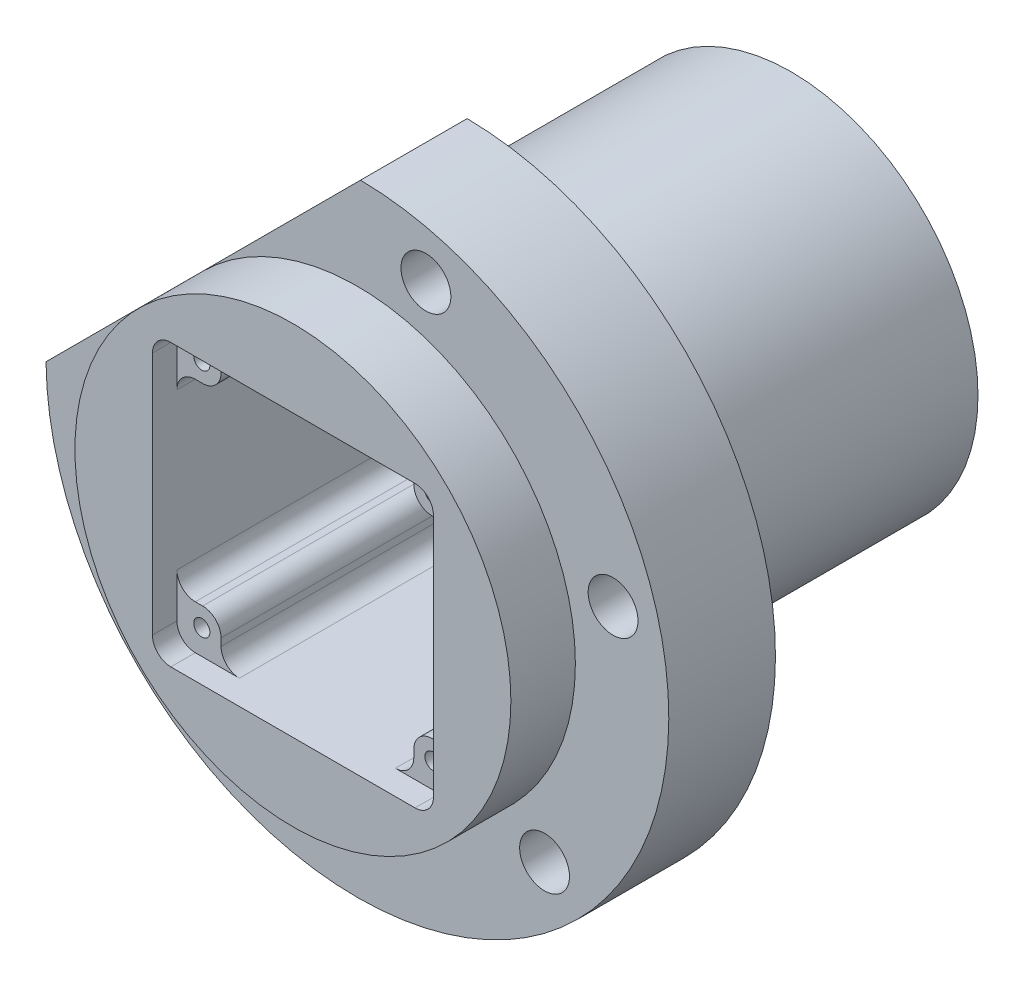
SolidWorks part; units mm, degrees
ref_plane "Front Plane" through (0, 0, 0) normal (0, 0, 1) x (1, 0, 0)
ref_plane "Top Plane" through (0, 0, 0) normal (0, 1, 0) x (1, 0, 0)
ref_plane "Right Plane" through (0, 0, 0) normal (1, 0, 0) x (0, 0, -1)
sketch "Sketch1" plane through (0, 0, 0) normal (0, 0, 1) x (1, 0, 0)
  circle A0 centre (0, 0) radius 44.45
  circle A1 centre (0, 0) radius 63.5
  dimension "D1" = 88.9
  dimension "D2" = 127
extrude "Boss-Extrude1" add sketch "Sketch1" along normal blind 6.35 contours A1 A0 | A0 region at (-61.7039, 0, 0)
extrude "Boss-Extrude2" add sketch "Sketch1<3>" against normal blind 101.6 from offset 19.5 contours A0 region at (0, 0, 0)
sketch "Sketch1<3>" plane through (0, 0, 0) normal (0, 0, 1) x (1, 0, 0) same geometry as "Sketch1"
sketch "Sketch2" plane through (0, 0, 19.5) normal (0, 0, -1) x (-1, 0, 0)
  line L0 (-19.65, 28.65) -> (-19.65, 19.65)
  line L1 (-28.65, -28.65) -> (28.65, -28.65) construction
  line L2 (-28.65, -28.65) -> (-28.65, 28.65) construction
  line L3 (-28.65, 28.65) -> (28.65, 28.65) construction
  line L4 (28.65, -28.65) -> (28.65, 28.65) construction
  line L5 (-28.65, -28.65) -> (28.65, 28.65) construction
  line L6 (-28.65, 28.65) -> (28.65, -28.65) construction
  line L7 (-19.65, 19.65) -> (-28.65, 19.65)
  line L8 (-28.65, 19.65) -> (-28.65, -19.65)
  line L9 (-28.65, -19.65) -> (-19.65, -19.65)
  line L10 (-19.65, -19.65) -> (-19.65, -28.65)
  line L11 (-19.65, -28.65) -> (19.65, -28.65)
  line L12 (19.65, -28.65) -> (19.65, -19.65)
  line L13 (19.65, -19.65) -> (28.65, -19.65)
  line L14 (28.65, -19.65) -> (28.65, 19.65)
  line L15 (28.65, 19.65) -> (19.65, 19.65)
  line L16 (19.65, 19.65) -> (19.65, 28.65)
  line L17 (19.65, 28.65) -> (-19.65, 28.65)
  point P0 (0, 0)
  dimension "D1" = 57.3
  dimension "D2" = 9
extrude "Cut-Extrude1" cut sketch "Sketch2" along normal through all
fillet "Fillet1" radius 3.75 12 edges at (19.65, -19.65, -31.3) (-19.65, -19.65, -31.3) (-19.65, 19.65, -31.3) (19.65, 19.65, -31.3) (-28.65, 19.65, -31.3) (-19.65, -28.65, -31.3) (19.65, -28.65, -31.3) (28.65, -19.65, -31.3) (28.65, 19.65, -31.3) (19.65, 28.65, -31.3) (-19.65, 28.65, -31.3) (-28.65, -19.65, -31.3)
sketch "Sketch3" plane through (0, 0, 19.5) normal (0, 0, -1) x (-1, 0, 0)
  line L1 (-24.9, -28.65) -> (24.9, -28.65)
  line L2 (-28.65, -24.9) -> (-28.65, 24.9)
  line L3 (-24.9, 28.65) -> (24.9, 28.65)
  line L4 (28.65, -24.9) -> (28.65, 24.9)
  line L5 (-28.65, -28.65) -> (28.65, 28.65) construction
  line L6 (-28.65, 28.65) -> (28.65, -28.65) construction
  arc A0 (-24.9, -28.65) -> (-28.65, -24.9) centre (-24.9, -24.9) cw
  arc A1 (24.9, -28.65) -> (28.65, -24.9) centre (24.9, -24.9) ccw
  arc A2 (24.9, 28.65) -> (28.65, 24.9) centre (24.9, 24.9) cw
  arc A3 (-28.65, 24.9) -> (-24.9, 28.65) centre (-24.9, 24.9) cw
  point P0 (0, 0)
  dimension "D2" = 3.75
  dimension "D1" = 57.3
extrude "Cut-Extrude2" cut sketch "Sketch3" along normal blind 5
sketch "Sketch4" plane through (0, 0, 0) normal (0, 0, -1) x (-1, 0, 0)
  circle A0 centre (0, 0) radius 44.45 construction
  circle A1 centre (0, 0) radius 63.5
  circle A2 centre (0, 0) radius 63.5
  circle A3 centre (0, 0) radius 44.45
  dimension "D1" = 0
extrude "Boss-Extrude3" add sketch "Sketch4" along normal blind 15.4
ref_plane "Plane1" through (0, 0, -7.4) normal (0, 0, -1) x (-1, 0, 0)
hole_wizard "CSK for #8 Flat Head Machine Screw1" positions "Sketch6" profile "Sketch7" countersink size "#8" standard "ANSI Inch" end condition through all
sketch "Sketch6" plane through (0, 0, -7.4) normal (0, 0, 1) x (1, 0, 0)
  line L0 (0, 0) -> (38.1661, -38.1661) construction
  line L2 (-24.9, 28.65) -> (24.9, 28.65) construction
  line L3 (31.4309, -31.4309) -> (44.9013, -44.9013) construction
  line L4 (0, 0) -> (38.1661, -38.1661) construction
  circle A0 centre (0, 0) radius 44.45 construction
  circle A1 centre (0, 0) radius 44.45 construction
  circle A4 centre (0, 0) radius 44.45 construction
  circle A5 centre (0, 0) radius 63.5
  circle A6 centre (0, 0) radius 63.5 construction
  point P0 (38.1661, -38.1661)
  point P45 (-13.9698, -52.1358)
  point P46 (-52.1358, -13.9698)
  point P47 (-38.1661, 38.1661)
  point P48 (13.9698, 52.1358)
  point P49 (52.1358, 13.9698)
  dimension "D1" = 45
  dimension "D2" = 6
sketch "Sketch7" plane through (38.1661, -38.1661, -7.4) normal (1, 0, 0) x (0, -1, 0)
  line L0 (0, 0) -> (0, 74.7)
  line L1 (0, 74.7) -> (2.2479, 74.7)
  line L2 (2.2479, 74.7) -> (2.2479, 3.2645)
  line L3 (2.2479, 3.2645) -> (5.0857, 0)
  line L5 (5.0857, 0) -> (0, 0)
  line L6 (-2.2479, 3.2645) -> (-5.0857, 0) construction
  line L11 (0, -6.35) -> (0, 107.95) construction
  dimension "Thru Hole Dia." = 4.4958
  dimension "Thru Hole Depth" = 74.7
  dimension "Near C'Sink Dia." = 10.1714
  dimension "Near C'Sink Angle" = 82
sketch "Sketch5" plane through (0, 0, 6.35) normal (0, 0, 1) x (1, 0, 0)
  line L0 (0.635, 63.4968) -> (-63.4968, -0.635)
  line L1 (-24.9, 28.65) -> (24.9, 28.65) construction
  circle A0 centre (0, 0) radius 63.5 construction
  circle A1 centre (0, 0) radius 44.45 construction
  circle A2 centre (0, 0) radius 63.5
  circle M3 centre (0, 0) radius 63.5
  dimension "D1" = 45
extrude "Cut-Extrude3" cut sketch "Sketch5" against normal through all contours L0 M3 region at (-36.895, 36.895, 6.35)
sketch "Sketch8" plane through (0, 0, -7.4) normal (0, 0, -1) x (-1, 0, 0)
  circle A4 centre (-38.1661, -38.1661) radius 5.0857 construction
  circle A9 centre (-38.1661, -38.1661) radius 5.0857
  circle A10 centre (52.1358, -13.9698) radius 5.0857 construction
  circle A11 centre (13.9698, -52.1358) radius 5.0857 construction
  circle A12 centre (-52.1358, 13.9698) radius 5.0857 construction
  circle A13 centre (-13.9698, 52.1358) radius 5.0857 construction
  circle A14 centre (52.1358, -13.9698) radius 5.0857
  circle A15 centre (13.9698, -52.1358) radius 5.0857
  circle A16 centre (-52.1358, 13.9698) radius 5.0857
  circle A17 centre (-13.9698, 52.1358) radius 5.0857
extrude "Cut-Extrude4" cut sketch "Sketch8" against normal through all
hole_wizard "Tap Drill for M4x0.7 Tap1" positions "Sketch10" profile "Sketch11" hole size "M4x0.7" standard "ANSI Metric" end condition through all
sketch "Sketch10" plane through (0, 0, 14.5) normal (0, 0, 1) x (1, 0, 0)
  point P0 (-23.57, 23.57)
  point P2 (23.57, 23.57)
  point P4 (23.57, -23.57)
  point P6 (-23.57, -23.57)
  point P10 (0, 0)
  point P11 (0, 0)
  point P12 (0, 0)
  point P13 (0, 0)
  dimension "D1" = 47.14
  dimension "D2" = 47.14
  dimension "D3" = 23.57
  dimension "D4" = 23.57
sketch "Sketch11" plane through (-23.57, 23.57, 14.5) normal (1, 0, 0) x (0, -1, 0)
  line L0 (0, 0) -> (0, 96.6)
  line L1 (0, 96.6) -> (1.65, 96.6)
  line L2 (1.65, 96.6) -> (1.65, 0)
  line L5 (1.65, 0) -> (0, 0)
  line L11 (0, -6.35) -> (0, 107.95) construction
  dimension "Thru Hole Dia." = 3.3
  dimension "Thru Hole Depth" = 96.6
sketch "Sketch12" plane through (0, 0, -82.1) normal (0, 0, -1) x (-1, 0, 0)
  circle A0 centre (0, 0) radius 38.1
  circle A1 centre (0, 0) radius 44.45 construction
  circle A2 centre (0, 0) radius 44.45
  dimension "D1" = 76.2
extrude "Cut-Extrude5" cut sketch "Sketch12" against normal up to surface (66.7 mm away) up to face at (49.8879, 13.9698, -15.4)
